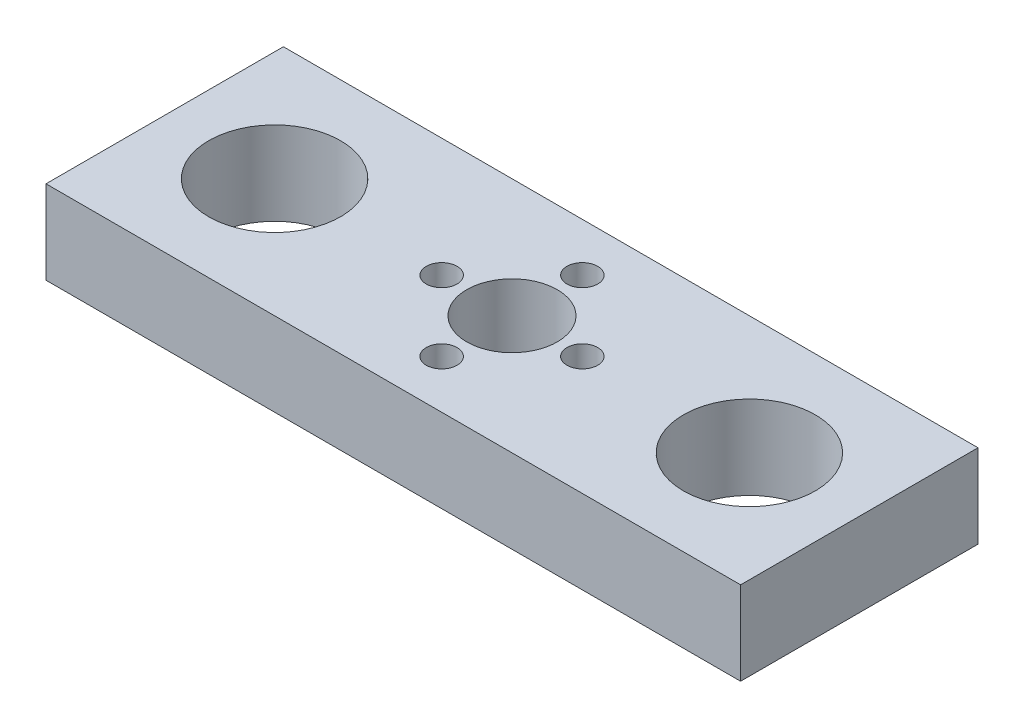
SolidWorks part; units mm, degrees
ref_plane "前视基准面" through (0, 0, 0) normal (0, 0, 1) x (1, 0, 0)
ref_plane "上视基准面" through (0, 0, 0) normal (0, 1, 0) x (1, 0, 0)
ref_plane "右视基准面" through (0, 0, 0) normal (1, 0, 0) x (0, 0, -1)
sketch "草图1" plane through (0, 0, 0) normal (0, 1, 0) x (1, 0, 0)
  line L1 (-39.5, 13.5) -> (39.5, 13.5)
  line L2 (-39.5, 13.5) -> (-39.5, -13.5)
  line L3 (-39.5, -13.5) -> (39.5, -13.5)
  line L4 (39.5, 13.5) -> (39.5, -13.5)
  line L5 (-39.5, 13.5) -> (39.5, -13.5) construction
  line L6 (-39.5, -13.5) -> (39.5, 13.5) construction
  point P0 (0, 0)
  dimension "D1" = 79
  dimension "D2" = 27
extrude "凸台-拉伸1" add sketch "草图1" along normal blind 9.5
sketch "草图2" plane through (0, 0, 0) normal (0, -1, 0) x (1, 0, 0)
  line L0 (-39.5, 0) -> (39.5, 0) construction
  line L1 (-39.5, -13.5) -> (-39.5, 13.5) construction
  line L2 (39.5, 13.5) -> (39.5, -13.5) construction
ref_plane "基准面1" through (0, 0, 0) normal (0, 0, 1) x (1, 0, 0)
sketch "草图3" plane through (0, 9.5, 0) normal (0, 1, 0) x (1, 0, 0)
  line L0 (-14.85, 0) -> (14.85, 0) construction
  line L1 (0, 13.5) -> (0, -13.5) construction
  line L2 (39.5, 13.5) -> (-39.5, 13.5) construction
  line L3 (-39.5, -13.5) -> (39.5, -13.5) construction
  circle A0 centre (-27, 0) radius 7.5
  circle A1 centre (27, 0) radius 7.5
  dimension "D1" = 15
  dimension "D2" = 54
extrude "切除-拉伸1" cut sketch "草图3" against normal through all contours A1 | A0
sketch "草图4" plane through (0, 9.5, 0) normal (0, 1, 0) x (1, 0, 0)
  line L0 (-39.5, 0) -> (39.5, 0) construction
  circle A0 centre (0, 0) radius 5.15
  dimension "D1" = 10.3
extrude "切除-拉伸2" cut sketch "草图4" against normal through all
sketch "草图5" plane through (0, 9.5, 0) normal (0, 1, 0) x (1, 0, 0)
  circle A4 centre (8, 0) radius 1.75
  circle A8 centre (-8, 0) radius 1.75
  circle A9 centre (0, 8) radius 1.75
  circle A10 centre (0, -8) radius 1.75
  dimension "D1" = 3.5
extrude "切除-拉伸3" cut sketch "草图5" against normal through all
ref_plane "基准面2" through (0, 4.5, 0) normal (0, 1, 0) x (1, 0, 0)
sketch "草图6" plane through (0, 4.5, 0) normal (0, 1, 0) x (1, 0, 0)
  line L0 (-39.5, 9.5) -> (39.5, 9.5) construction
  line L1 (-39.5, 13.5) -> (-39.5, -13.5) construction
  line L2 (39.5, -13.5) -> (39.5, 13.5) construction
  line L3 (-39.5, -9.5) -> (39.5, -9.5) construction
  line L4 (-39.5, -13.5) -> (39.5, -13.5) construction
  line L5 (39.5, 13.5) -> (-39.5, 13.5) construction
  dimension "D1" = 4
  dimension "D2" = 4
